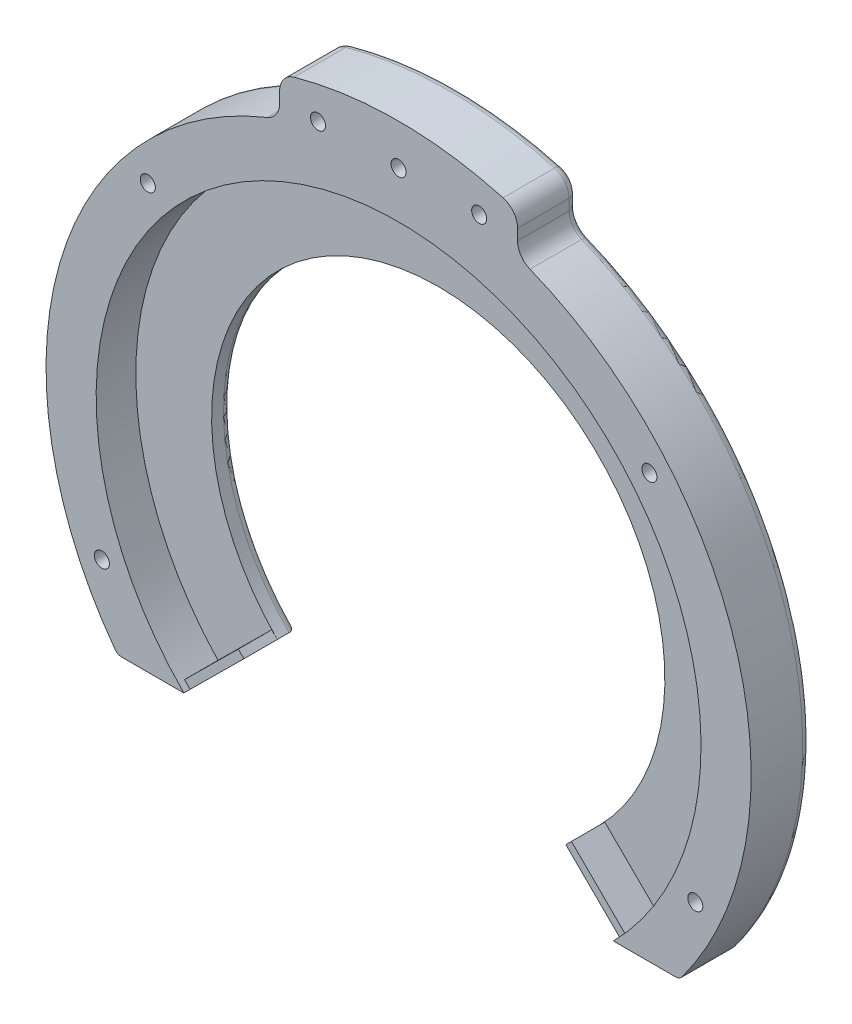
SolidWorks part; units mm, degrees
material "ABS"
ref_plane "Front Plane" through (0, 0, 0) normal (0, 0, 1) x (1, 0, 0)
ref_plane "Top Plane" through (0, 0, 0) normal (0, 1, 0) x (1, 0, 0)
ref_plane "Right Plane" through (0, 0, 0) normal (1, 0, 0) x (0, 0, -1)
sketch "Sketch1" plane through (0, 0, 0) normal (0, 0, 1) x (1, 0, 0)
  line L0 (0, 0) -> (0, 98.2845) construction
  line L1 (0, 98.2845) -> (-30, 98.2845) construction
  line L2 (0, 98.2845) -> (30, 98.2845) construction
  line L3 (30, 98.2845) -> (30, 83.6852) construction
  line L4 (-30, 98.2845) -> (-30, 83.6852) construction
  line L5 (-30, 83.6852) -> (-30, 93.594)
  line L6 (30, 83.6852) -> (30, 93.594)
  line L7 (0, 0) -> (-62.2819, 0) construction
  line L8 (0, 0) -> (62.2819, 0) construction
  line L9 (-62.2819, 0) -> (-62.2819, 44.0124) construction
  line L10 (62.2819, 0) -> (62.2819, 44.0124) construction
  line L11 (0, 0) -> (-62.2819, 44.0124) construction
  line L12 (0, 0) -> (62.2819, 44.0124) construction
  line L13 (0, 0) -> (-63.1328, -62.5897) construction
  line L14 (0, 0) -> (63.1328, -62.5897) construction
  line L15 (-54.1589, -53.693) -> (-70.8539, -53.693)
  line L16 (54.1589, -53.693) -> (70.8539, -53.693)
  line L17 (-54.1589, -53.693) -> (-40.5853, -40.2362)
  line L18 (54.1589, -53.693) -> (40.5853, -40.2362)
  circle A0 centre (0, 0) radius 88.9
  circle A1 centre (0, 0) radius 76.2635
  circle A2 centre (0, 0) radius 57.15
  arc A3 (30, 93.594) -> (-30, 93.594) centre (0, 0) ccw
  point P16 (-54.1589, -53.693)
  point P19 (54.1589, -53.693)
  dimension "D1" = 177.8
  dimension "D2" = 152.527
  dimension "D3" = 114.3
  dimension "D4" = 30
  dimension "D6" = 14.5993
  dimension "D5" = 30
  dimension "D7" = 54.752
  dimension "D8" = 54.752
  dimension "D9" = 80
  dimension "D10" = 80
extrude "Boss-Extrude1" add sketch "Sketch1" along normal blind 5 contours A2 L18 A1 L17 | A1 L16 A0 L15 region at (0, 86.6208, 0) region at (-28.2697, 68.6682, 0)
extrude "Boss-Extrude2" add sketch "Sketch1<3>" along normal blind 15 contours A1 L16 A0 L15 region at (0, 86.6208, 0)
sketch "Sketch1<3>" plane through (0, 0, 0) normal (0, 0, 1) x (1, 0, 0) same geometry as "Sketch1"
extrude "Boss-Extrude3" add sketch "Sketch1<4>" along normal blind 15 contours L6 A3 L5 A0 region at (0, 91.9357, 0)
sketch "Sketch1<4>" plane through (0, 0, 0) normal (0, 0, 1) x (1, 0, 0) same geometry as "Sketch1"
hole_wizard "#6 Clearance Hole2" positions "3DSketch1" profile "Sketch2" hole size "#6" standard "ANSI Inch" end condition through all
sketch3d "3DSketch1"
  line L0 (54.1589, -53.693, 0) -> (-54.1589, -53.693, 0) construction
  line L1 (0, 0, 0) -> (0, -53.693, 0) construction
  line L2 (0, 0, 0) -> (80.5708, -37.5708, 0) construction
  line L3 (0, 0, 0) -> (68.1014, 57.1438, 0) construction
  line L4 (0, 0, 0) -> (-68.1014, 57.1438, 0) construction
  line L5 (0, 0, 0) -> (-80.5708, -37.5708, 0) construction
  arc A0 (70.8539, -53.693, 0) -> (30, 83.6852, 0) centre (0, 0, 0) ccw construction
  arc A1 (-30, 83.6852, 0) -> (-70.8539, -53.693, 0) centre (0, 0, 0) ccw construction
  circle A2 centre (0, 0, 0) radius 82.55
  point P0 (74.8157, -34.8871, 0)
  point P2 (63.237, 53.0621, 0)
  point P4 (-63.237, 53.0621, 0)
  point P6 (-74.8157, -34.8871, 0)
  point P22 (0, 0, 88.9)
  point P30 (0, 0, 88.9)
  point P36 (0, 0, 82.55)
  dimension "D5" = 165.1
  dimension "D1" = 65
  dimension "D2" = 130
  dimension "D3" = 65
  dimension "D4" = 130
sketch "Sketch2" plane through (74.8157, -34.8871, 0) normal (1, 0, 0) x (0, 1, 0)
  line L0 (0, 0) -> (0, 15)
  line L1 (0, 15) -> (1.8986, 15)
  line L2 (1.8986, 15) -> (1.8986, 0)
  line L5 (1.8986, 0) -> (0, 0)
  line L11 (0, -6.35) -> (0, 107.95) construction
  dimension "Thru Hole Dia." = 3.7973
  dimension "Thru Hole Depth" = 15
hole_wizard "#6 Clearance Hole1" positions "3DSketch2" profile "Sketch3" hole size "#6" standard "ANSI Inch" end condition through all
sketch3d "3DSketch2"
  line L0 (0, 0, 0) -> (0, 98.2845, 0) construction
  line L1 (0, 88, 0) -> (-20.32, 88, 0) construction
  line L2 (0, 88, 0) -> (20.32, 88, 0) construction
  arc A0 (30, 93.594, 0) -> (-30, 93.594, 0) centre (0, 0, 0) ccw construction
  circle A1 centre (0, 0, 0) radius 95
  circle A2 centre (0, 0, 0) radius 85
  circle A3 centre (0, 0, 0) radius 88
  point P0 (0, 88, 0)
  point P2 (-20.32, 88, 0)
  point P4 (20.32, 88, 0)
  point P13 (0, 0, 98.2845)
  point P17 (0, 0, 95)
  point P20 (0, 0, 85)
  point P23 (0, 0, 88)
  dimension "D1" = 190
  dimension "D2" = 176
  dimension "D3" = 170
  dimension "D4" = 20.32
  dimension "D5" = 20.32
sketch "Sketch3" plane through (0, 88, 0) normal (1, 0, 0) x (0, 1, 0)
  line L0 (0, 0) -> (0, 15)
  line L1 (0, 15) -> (1.8986, 15)
  line L2 (1.8986, 15) -> (1.8986, 0)
  line L5 (1.8986, 0) -> (0, 0)
  line L11 (0, -6.35) -> (0, 107.95) construction
  dimension "Thru Hole Dia." = 3.7973
  dimension "Thru Hole Depth" = 15
sketch "Sketch4" plane through (0, 0, 0) normal (0, 0, -1) x (-1, 0, 0)
  line L0 (-74.8157, -34.8871) -> (-79.5657, -34.8871) construction
  line L1 (-74.8157, -34.8871) -> (-77.1907, -30.7735) construction
  line L2 (-74.8157, -34.8871) -> (-72.4407, -30.7735) construction
  line L3 (-74.8157, -34.8871) -> (-70.0657, -34.8871) construction
  line L4 (-74.8157, -34.8871) -> (-77.1907, -39.0008) construction
  line L5 (-74.8157, -34.8871) -> (-72.4407, -39.0008) construction
  line L6 (-79.5657, -34.8871) -> (-77.1907, -30.7735)
  line L7 (-77.1907, -30.7735) -> (-72.4407, -30.7735)
  line L8 (-72.4407, -30.7735) -> (-70.0657, -34.8871)
  line L9 (-70.0657, -34.8871) -> (-72.4407, -39.0008)
  line L10 (-72.4407, -39.0008) -> (-77.1907, -39.0008)
  line L11 (-77.1907, -39.0008) -> (-79.5657, -34.8871)
  line L12 (-63.237, 53.0621) -> (-67.987, 53.0621) construction
  line L13 (-63.237, 53.0621) -> (-65.612, 57.1757) construction
  line L14 (-63.237, 53.0621) -> (-60.862, 57.1757) construction
  line L15 (-63.237, 53.0621) -> (-58.487, 53.0621) construction
  line L16 (-63.237, 53.0621) -> (-65.612, 48.9485) construction
  line L17 (-63.237, 53.0621) -> (-60.862, 48.9485) construction
  line L18 (-67.987, 53.0621) -> (-65.612, 48.9485)
  line L19 (-65.612, 48.9485) -> (-60.862, 48.9485)
  line L20 (-60.862, 48.9485) -> (-58.487, 53.0621)
  line L21 (-58.487, 53.0621) -> (-60.862, 57.1757)
  line L22 (-60.862, 57.1757) -> (-65.612, 57.1757)
  line L23 (-65.612, 57.1757) -> (-67.987, 53.0621)
  line L24 (63.237, 53.0621) -> (58.487, 53.0621) construction
  line L25 (63.237, 53.0621) -> (60.862, 57.1757) construction
  line L26 (63.237, 53.0621) -> (65.612, 57.1757) construction
  line L27 (63.237, 53.0621) -> (67.987, 53.0621) construction
  line L28 (63.237, 53.0621) -> (60.862, 48.9485) construction
  line L29 (63.237, 53.0621) -> (65.612, 48.9485) construction
  line L30 (58.487, 53.0621) -> (60.862, 48.9485)
  line L31 (60.862, 48.9485) -> (65.612, 48.9485)
  line L32 (65.612, 48.9485) -> (67.987, 53.0621)
  line L33 (67.987, 53.0621) -> (65.612, 57.1757)
  line L34 (65.612, 57.1757) -> (60.862, 57.1757)
  line L35 (60.862, 57.1757) -> (58.487, 53.0621)
  line L36 (74.8157, -34.8871) -> (70.0657, -34.8871) construction
  line L37 (74.8157, -34.8871) -> (72.4407, -30.7735) construction
  line L38 (74.8157, -34.8871) -> (77.1907, -30.7735) construction
  line L39 (74.8157, -34.8871) -> (79.5657, -34.8871) construction
  line L40 (74.8157, -34.8871) -> (77.1907, -39.0008) construction
  line L41 (74.8157, -34.8871) -> (72.4407, -39.0008) construction
  line L42 (72.4407, -30.7735) -> (70.0657, -34.8871)
  line L43 (70.0657, -34.8871) -> (72.4407, -39.0008)
  line L44 (72.4407, -39.0008) -> (77.1907, -39.0008)
  line L45 (77.1907, -39.0008) -> (79.5657, -34.8871)
  line L46 (79.5657, -34.8871) -> (77.1907, -30.7735)
  line L47 (77.1907, -30.7735) -> (72.4407, -30.7735)
  dimension "D1" = 60
  dimension "D2" = 60
  dimension "D3" = 60
  dimension "D4" = 4.75
  dimension "D5" = 4.75
  dimension "D6" = 60
  dimension "D7" = 60
  dimension "D8" = 60
  dimension "D9" = 60
  dimension "D10" = 4.75
  dimension "D11" = 4.75
  dimension "D12" = 60
  dimension "D13" = 60
  dimension "D14" = 60
  dimension "D15" = 60
  dimension "D16" = 4.75
  dimension "D17" = 4.75
  dimension "D18" = 60
  dimension "D19" = 60
  dimension "D20" = 60
  dimension "D21" = 60
  dimension "D22" = 4.75
  dimension "D23" = 4.75
extrude "Cut-Extrude1" cut sketch "Sketch4" against normal blind 3.05
sketch "Sketch5" plane through (0, 0, 0) normal (0.704, -0.7102, 0) x (0.7102, 0.704, 0)
  line L0 (-57.15, 5) -> (-57.15, 9)
  line L1 (-76.2635, 15) -> (-57.15, 15)
  line L2 (-76.2635, 9) -> (-76.2635, 15)
  line L3 (-57.15, 9) -> (-57.15, 15)
  line L4 (-76.2635, 15) -> (-76.2635, 5) construction
  line L5 (-76.2635, 5) -> (-57.15, 5)
  line L6 (-76.2635, 9) -> (-76.2635, 5)
  line L7 (-76.2635, 13.4125) -> (-57.15, 13.4125)
  line M3 (-57.15, 5) -> (-76.2635, 5)
  dimension "D1" = 4
  dimension "D2" = 1.5875
extrude "Boss-Extrude4" add sketch "Sketch5" against normal blind 2 contours L7 L2 L6 L0 L3 M3 region at (-47.3721, -46.9646, 9.2063)
sketch "Sketch6" plane through (0, 0, 0) normal (-0.704, -0.7102, 0) x (0.7102, -0.704, 0)
  line L0 (76.2635, 5) -> (57.15, 5)
  line L1 (76.2635, 15) -> (57.15, 15)
  line L2 (57.15, 13.4125) -> (76.2635, 13.4125)
  line L3 (76.2635, 15) -> (76.2635, 5) construction
  line L4 (57.15, 5) -> (57.15, 9)
  line L5 (76.2635, 9) -> (76.2635, 5)
  line L6 (57.15, 9) -> (57.15, 15)
  line L7 (76.2635, 15) -> (76.2635, 9)
  line M3 (76.2635, 5) -> (57.15, 5)
  dimension "D1" = 4
  dimension "D2" = 1.5875
extrude "Boss-Extrude5" add sketch "Sketch6" against normal blind 2 contours L7 L2 L6 L4 L5 M3 region at (47.3721, -46.9646, 9.2062)
fillet "Fillet1" radius 5 4 edges at (-30, 83.6852, 7.5) (-30, 93.594, 7.5) (30, 93.594, 7.5) (30, 83.6852, 7.5)
fillet "Fillet2" radius 2 16 edges at (-85.6749, 23.7281, 0) (-30.8576, 84.3331, 0) (-30, 88.5027, 0) (-28.9812, 92.897, 0) (0, 98.2845, 0) (28.9812, 92.897, 0) (30, 88.5027, 0) (30.8576, 84.3331, 0) (0, 57.15, 0) (85.6749, 23.7281, 0) (-70.8539, -53.693, 7.5) (-62.5064, -53.693, 0) (-47.3721, -46.9646, 0) (70.8539, -53.693, 7.5) (47.3721, -46.9646, 0) (62.5064, -53.693, 0)
